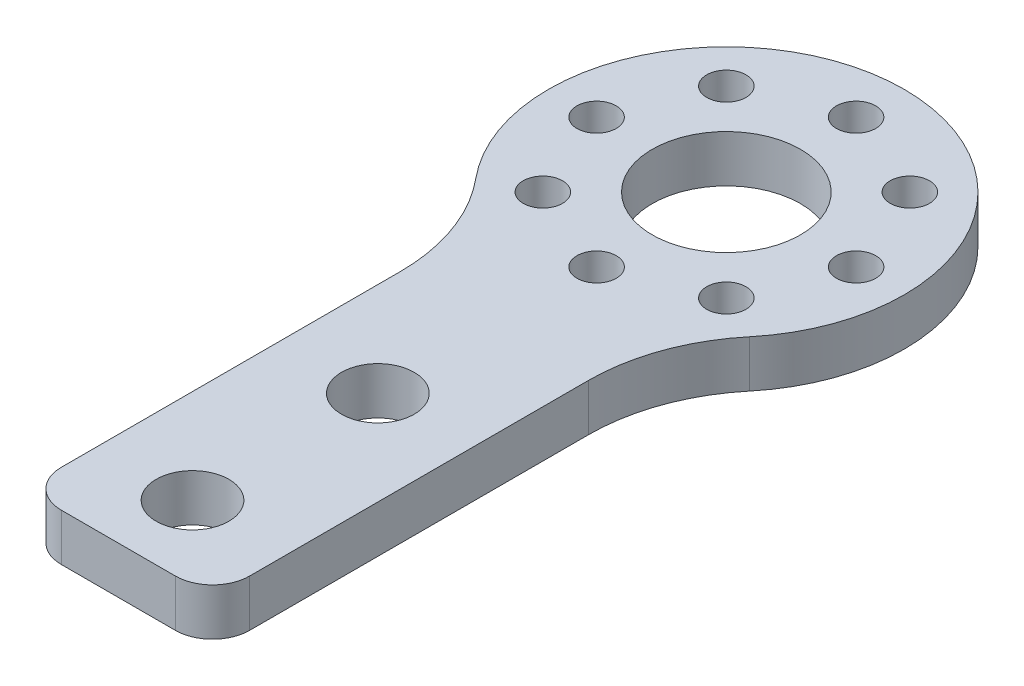
SolidWorks part; units mm, degrees
material "1060 Alloy"
ref_plane "Front Plane" through (0, 0, 0) normal (0, 0, 1) x (1, 0, 0)
ref_plane "Top Plane" through (0, 0, 0) normal (0, 1, 0) x (1, 0, 0)
ref_plane "Right Plane" through (0, 0, 0) normal (1, 0, 0) x (0, 0, -1)
sketch "Sketch1" plane through (0, 0, 0) normal (0, 1, 0) x (1, 0, 0)
  line L0 (-12.7, -82) -> (12.7, -82)
  line L1 (12.7, -82) -> (12.7, -20.3644)
  line L2 (-12.7, -82) -> (-12.7, -20.3644)
  line L3 (0, -82) -> (0, -47) construction
  arc A0 (12.7, -20.3644) -> (-12.7, -20.3644) centre (0, 0) ccw
  point P5 (0, -82)
  point P9 (0, -72)
  point P11 (0, -47)
  dimension "D2" = 48
  dimension "D1" = 25.4
  dimension "D3" = 47
  dimension "D4" = 25
  dimension "D5" = 10
extrude "Boss-Extrude1" add sketch "Sketch1" along normal blind 6.35 contours A0 L2 L0 L1
sketch "Sketch2" plane through (0, 0, 0) normal (0, -1, 0) x (1, 0, 0)
  circle A0 centre (0, 0) radius 17.5 construction
  point P3 (17.5, 0)
  point P6 (12.3744, -12.3744)
  point P7 (0, -17.5)
  point P8 (-12.3744, -12.3744)
  point P9 (-17.5, 0)
  point P10 (-12.3744, 12.3744)
  point P11 (0, 17.5)
  point P12 (12.3744, 12.3744)
  point P13 (0, 0)
  dimension "D2" = 35
  dimension "D1" = 8
hole_wizard "M5 Clearance Hole1" positions "Sketch3" profile "Sketch4" hole size "M5" standard "ANSI Metric" end condition through all
sketch "Sketch3" plane through (0, 0, 0) normal (0, -1, 0) x (-1, 0, 0)
  point P0 (0, 17.5)
  point P3 (12.3744, 12.3744)
  point P6 (17.5, 0)
  point P9 (12.3744, -12.3744)
  point P12 (0, -17.5)
  point P15 (-12.3744, -12.3744)
  point P18 (-17.5, 0)
  point P21 (-12.3744, 12.3744)
sketch "Sketch4" plane through (0, 0, -17.5) normal (1, 0, 0) x (0, 0, -1)
  line L0 (0, 0) -> (0, 6.35)
  line L1 (0, 6.35) -> (2.65, 6.35)
  line L2 (2.65, 6.35) -> (2.65, 0)
  line L5 (2.65, 0) -> (0, 0)
  line L11 (0, -6.35) -> (0, 107.95) construction
  dimension "Thru Hole Dia." = 5.3
  dimension "Thru Hole Depth" = 6.35
sketch "Sketch5" plane through (0, 0, 0) normal (0, -1, 0) x (1, 0, 0)
  circle A0 centre (0, 0) radius 10
  dimension "D1" = 20
extrude "Cut-Extrude1" cut sketch "Sketch5" against normal through all
fillet "Fillet1" radius 25 2 edges at (-12.7, 3.175, 20.3644) (12.7, 3.175, 20.3644)
fillet "Fillet2" radius 5 2 edges at (12.7, 3.175, 82) (-12.7, 3.175, 82)
hole_wizard "3/8 Clearance Hole1" positions "Sketch9" profile "Sketch10" hole size "3/8" standard "ANSI Inch" end condition through all
sketch "Sketch9" plane through (0, 0, 0) normal (0, -1, 0) x (-1, 0, 0)
  point P0 (0, -47)
  point P3 (0, -72)
sketch "Sketch10" plane through (0, 0, 47) normal (1, 0, 0) x (0, 0, -1)
  line L0 (0, 0) -> (0, 6.35)
  line L1 (0, 6.35) -> (4.9022, 6.35)
  line L2 (4.9022, 6.35) -> (4.9022, 0)
  line L5 (4.9022, 0) -> (0, 0)
  line L11 (0, -6.35) -> (0, 107.95) construction
  dimension "Thru Hole Dia." = 9.8044
  dimension "Thru Hole Depth" = 6.35
ref_axis "Axis1" through (0, -0.3175, 0) along (0, 1, 0)
